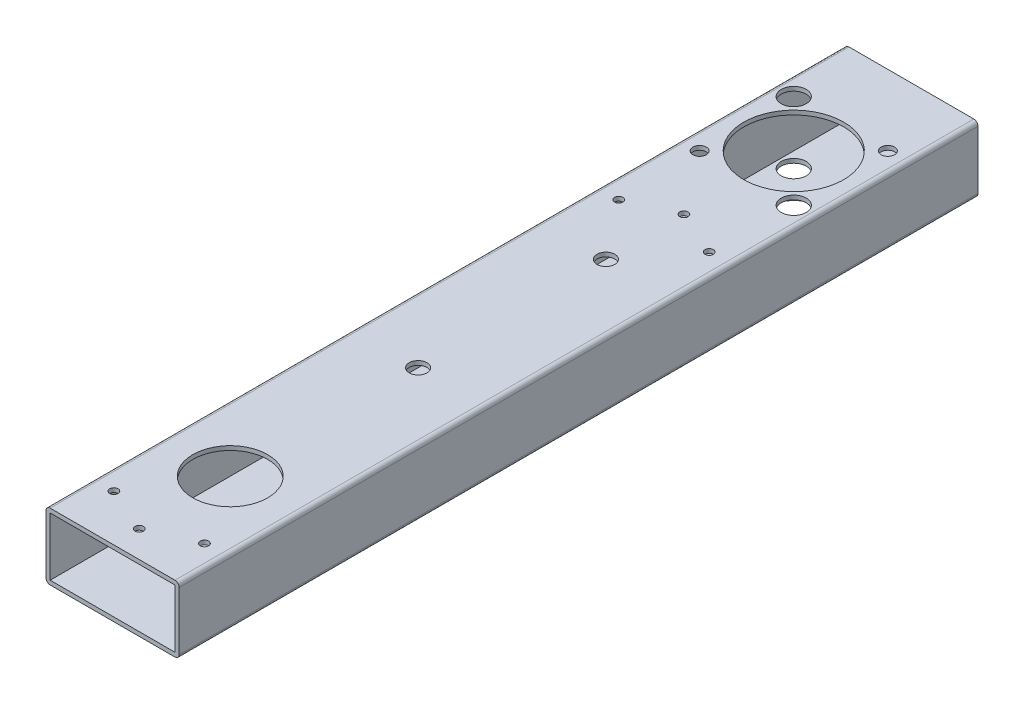
SolidWorks part; units mm, degrees
ref_plane "Front Plane" through (0, 0, 0) normal (0, 0, 1) x (1, 0, 0)
ref_plane "Top Plane" through (0, 0, 0) normal (0, 1, 0) x (1, 0, 0)
ref_plane "Right Plane" through (0, 0, 0) normal (1, 0, 0) x (0, 0, -1)
sketch "Sketch1" plane through (0, 0, 0) normal (0, 0, 1) x (1, 0, 0)
  line L0 (-23.8125, 11.1125) -> (23.8125, 11.1125)
  line L1 (-23.8125, -12.7) -> (23.8125, -12.7)
  line L2 (-25.4, -11.1125) -> (-25.4, 11.1125)
  line L3 (-23.8125, 12.7) -> (23.8125, 12.7)
  line L4 (25.4, -11.1125) -> (25.4, 11.1125)
  line L5 (-25.4, -12.7) -> (25.4, 12.7) construction
  line L6 (-25.4, 12.7) -> (25.4, -12.7) construction
  line L7 (23.8125, -11.1125) -> (23.8125, 11.1125)
  line L8 (-23.8125, -11.1125) -> (23.8125, -11.1125)
  line L9 (-23.8125, -11.1125) -> (-23.8125, 11.1125)
  line L10 (-25.4, -12.7) -> (25.4, -12.7) construction
  line L11 (-25.4, -12.7) -> (-25.4, 12.7) construction
  line L12 (25.4, -12.7) -> (25.4, 12.7) construction
  line L13 (-25.4, 12.7) -> (25.4, 12.7) construction
  arc A0 (-23.8125, -12.7) -> (-25.4, -11.1125) centre (-23.8125, -11.1125) cw
  arc A1 (23.8125, -12.7) -> (25.4, -11.1125) centre (23.8125, -11.1125) ccw
  arc A2 (23.8125, 12.7) -> (25.4, 11.1125) centre (23.8125, 11.1125) cw
  arc A3 (-25.4, 11.1125) -> (-23.8125, 12.7) centre (-23.8125, 11.1125) cw
  point P0 (0, 0)
  dimension "D4" = 1.5875
  dimension "D1" = 25.4
  dimension "D2" = 50.8
  dimension "D3" = 1.5875
extrude "Boss-Extrude1" add sketch "Sketch1" along normal blind 304.8
sketch "Sketch2" plane through (0, 12.7, 0) normal (0, 1, 0) x (1, 0, 0)
  line L0 (0, -259.9) -> (0, -304.8) construction
  line L1 (23.8125, -304.8) -> (-23.8125, -304.8) construction
  line L4 (0, -259.9) -> (0, -44.9) construction
  line L7 (0, -44.9) -> (0, 0) construction
  line L8 (23.8125, 0) -> (-23.8125, 0) construction
  circle A10 centre (0, -259.9) radius 14.2875
  circle A11 centre (0, -44.9) radius 19.05
  dimension "D1" = 38.1
  dimension "D4" = 215
  dimension "D2" = 28.575
extrude "Cut-Extrude1" cut sketch "Sketch2" against normal up to next and the other way through all
sketch "Sketch3" plane through (0, -12.7, 0) normal (0, -1, 0) x (1, 0, 0)
  circle A0 centre (0, 44.9) radius 12.7
  circle A1 centre (0, 259.9) radius 12.7
  circle A7 centre (0, 259.9) radius 14.2875 construction
  circle A8 centre (0, 44.9) radius 19.05 construction
  dimension "D1" = 25.4
  dimension "D2" = 25.4
extrude "Cut-Extrude2" cut sketch "Sketch3" against normal up to next and the other way through all
sketch "Sketch7" plane through (0, 11.1125, 0) normal (0, -1, 0) x (1, 0, 0)
  arc A16 (20.5132, 26.9395) -> (15.4078, 26.9395) centre (17.9605, 26.9395) ccw construction
  arc A17 (15.4078, 26.9395) -> (20.5132, 26.9395) centre (17.9605, 26.9395) ccw construction
  arc A18 (-15.4078, 62.8605) -> (-20.5132, 62.8605) centre (-17.9605, 62.8605) ccw construction
  arc A19 (-20.5132, 62.8605) -> (-15.4078, 62.8605) centre (-17.9605, 62.8605) ccw construction
  arc A20 (20.5132, 26.9395) -> (15.4078, 26.9395) centre (17.9605, 26.9395) ccw
  arc A21 (15.4078, 26.9395) -> (20.5132, 26.9395) centre (17.9605, 26.9395) ccw
  arc A22 (-15.4078, 62.8605) -> (-20.5132, 62.8605) centre (-17.9605, 62.8605) ccw
  arc A23 (-20.5132, 62.8605) -> (-15.4078, 62.8605) centre (-17.9605, 62.8605) ccw
  arc A32 (-15.4078, 26.9395) -> (-20.5132, 26.9395) centre (-17.9605, 26.9395) ccw construction
  arc A33 (-20.5132, 26.9395) -> (-15.4078, 26.9395) centre (-17.9605, 26.9395) ccw construction
  arc A34 (15.4078, 62.8605) -> (20.5132, 62.8605) centre (17.9605, 62.8605) ccw construction
  arc A35 (20.5132, 62.8605) -> (15.4078, 62.8605) centre (17.9605, 62.8605) ccw construction
  arc A36 (-15.4078, 26.9395) -> (-20.5132, 26.9395) centre (-17.9605, 26.9395) ccw construction
  arc A37 (-20.5132, 26.9395) -> (-15.4078, 26.9395) centre (-17.9605, 26.9395) ccw construction
  arc A38 (15.4078, 62.8605) -> (20.5132, 62.8605) centre (17.9605, 62.8605) ccw construction
  arc A39 (20.5132, 62.8605) -> (15.4078, 62.8605) centre (17.9605, 62.8605) ccw construction
  circle A40 centre (17.9605, 62.8605) radius 4.7625
  circle A41 centre (-17.9605, 26.9395) radius 4.7625
  dimension "D2" = 9.525
extrude "Cut-Extrude3" cut sketch "Sketch7" against normal through all and the other way through all
sketch "Sketch8" plane through (0, 12.7, 0) normal (0, 1, 0) x (1, 0, 0)
  line L0 (0, -44.9) -> (0, -259.9) construction
  circle A0 centre (0, -116.5667) radius 3.3782
  circle A2 centre (0, -188.2333) radius 3.3782
  dimension "D1" = 6.7564
  dimension "D2" = 71.6667
  dimension "D3" = 71.6667
extrude "Cut-Extrude4" cut sketch "Sketch8" against normal up to next and the other way through all
sketch "Sketch9" plane through (0, -12.7, 0) normal (0, -1, 0) x (1, 0, 0)
  line L0 (0, 44.9) -> (0, 259.9) construction
  circle A0 centre (0, 116.5667) radius 7.9375
  circle A2 centre (0, 116.5667) radius 3.3782 construction
  circle A4 centre (0, 188.2333) radius 7.9375
  circle A5 centre (0, 188.2333) radius 3.3782 construction
  dimension "D1" = 15.875
extrude "Cut-Extrude5" cut sketch "Sketch9" against normal up to next and the other way through all
sketch "Sketch10" plane through (0, 12.7, 0) normal (0, 1, 0) x (1, 0, 0)
  circle A0 centre (17.272, -287.02) radius 1.5875 construction
  circle A1 centre (-17.272, -287.02) radius 1.5875 construction
  circle A2 centre (0, -294.64) radius 1.5875 construction
  circle A3 centre (17.272, -94.43) radius 1.5875 construction
  circle A4 centre (0, -86.81) radius 1.5875 construction
  circle A5 centre (-17.272, -94.43) radius 1.5875 construction
  circle A6 centre (17.272, -287.02) radius 1.5875
  circle A7 centre (-17.272, -287.02) radius 1.5875
  circle A8 centre (0, -294.64) radius 1.5875
  circle A9 centre (17.272, -94.43) radius 1.5875
  circle A10 centre (0, -86.81) radius 1.5875
  circle A11 centre (-17.272, -94.43) radius 1.5875
extrude "Cut-Extrude6" cut sketch "Sketch10" against normal up to next and the other way through all
